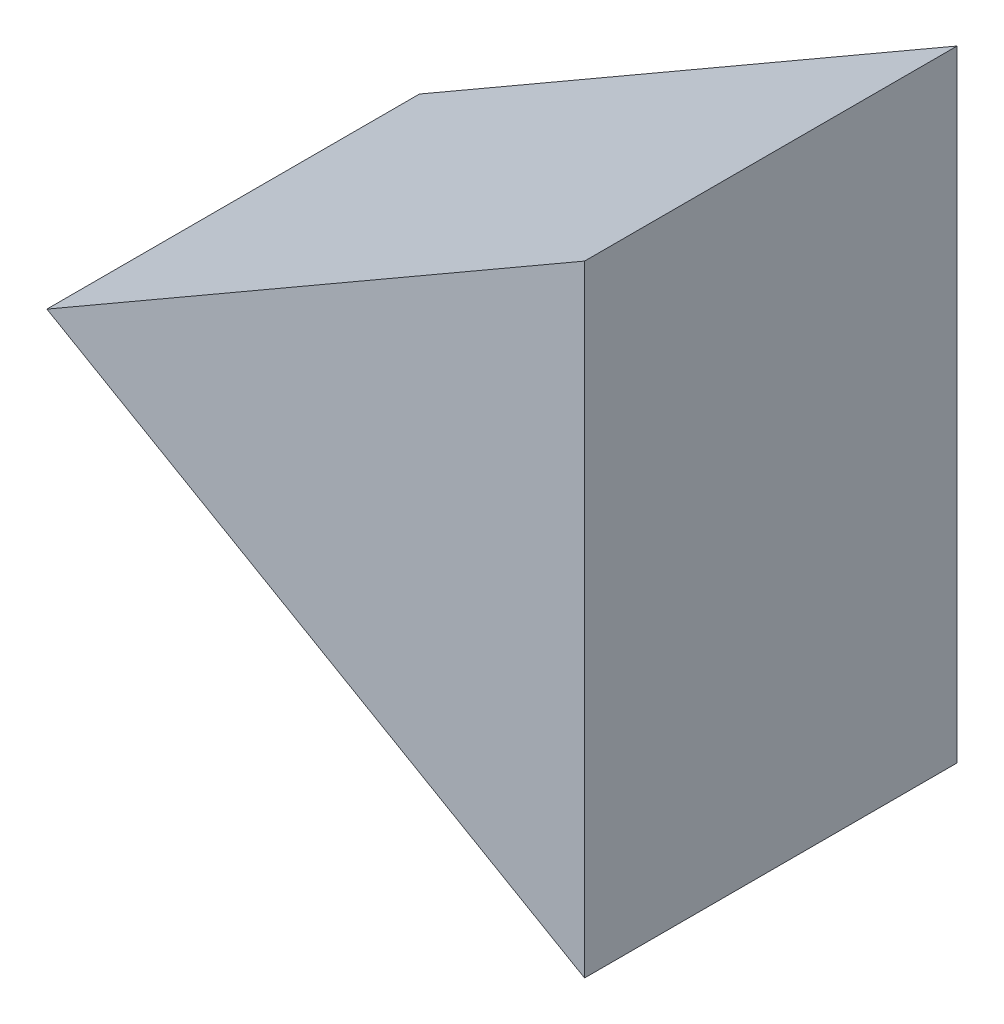
SolidWorks part; units mm, degrees
ref_plane "正面"
ref_plane "平面" through (0, 0, 0) normal (0, 1, 0) x (1, 0, 0)
ref_plane "右側面" through (0, 0, 0) normal (1, 0, 0) x (0, 0, -1)
sketch "ｽｹｯﾁ1" plane through (0, 0, 0) normal (0, 0, 1) x (1, 0, 0)
  line L0 (0, 0) -> (866.0254, 500)
  line L1 (866.0254, 500) -> (866.0254, -500)
  line L2 (866.0254, -500) -> (0, 0)
  line L3 (0, 0) -> (866.0254, 0)
  line L4 (433.0127, 0) -> (-2066.9873, 4330.127)
  dimension "D1" = 30
  dimension "D2" = 30
  dimension "D3" = 1000
extrude "ﾎﾞｽ - 押し出し1" add sketch "ｽｹｯﾁ1" along normal blind 300 and the other way blind 300 contours L0 L1 L2
